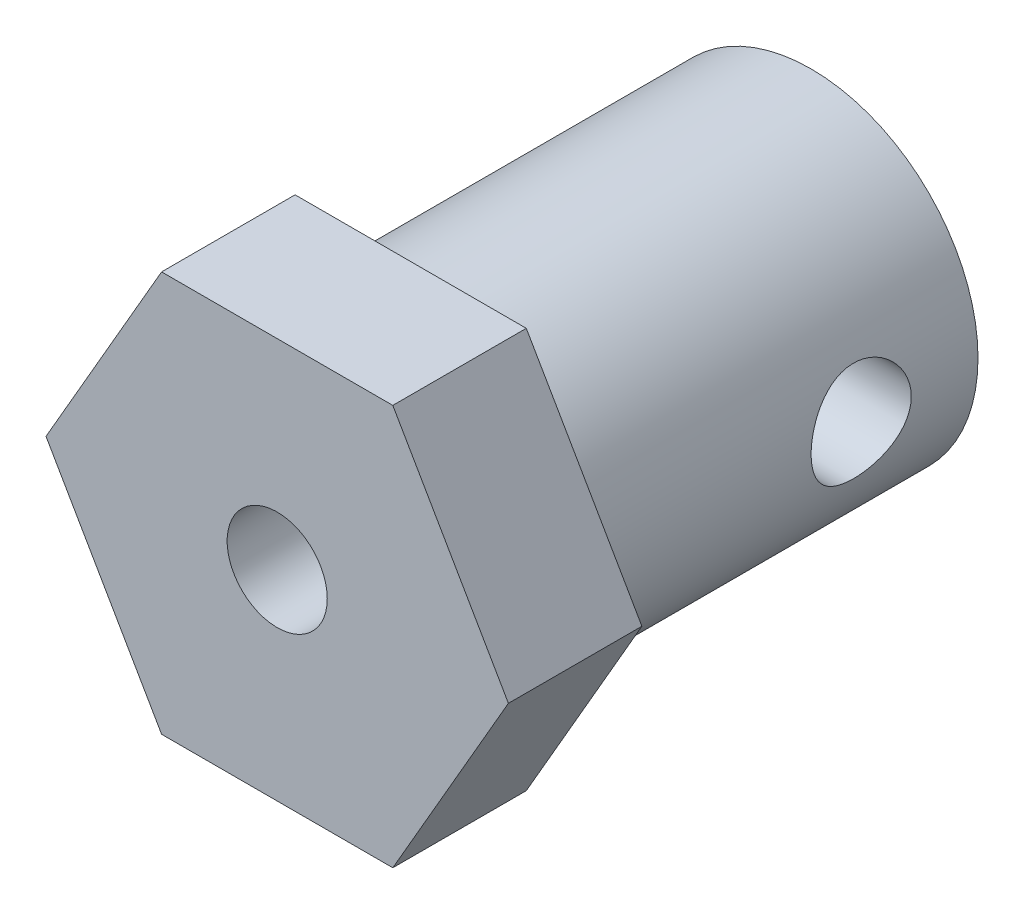
SolidWorks part; units mm, degrees
ref_plane "Alzado" through (0, 0, 0) normal (0, 0, 1) x (1, 0, 0)
ref_plane "Planta" through (0, 0, 0) normal (0, 1, 0) x (1, 0, 0)
ref_plane "Vista lateral" through (0, 0, 0) normal (1, 0, 0) x (0, 0, -1)
sketch "Croquis2" plane through (0, 0, 0) normal (0, 0, 1) x (1, 0, 0)
  line L1 (3.4641, 6) -> (-3.4641, 6)
  line L2 (-3.4641, 6) -> (-6.9282, 0)
  line L3 (-6.9282, 0) -> (-3.4641, -6)
  line L4 (-3.4641, -6) -> (3.4641, -6)
  line L5 (3.4641, -6) -> (6.9282, 0)
  line L6 (6.9282, 0) -> (3.4641, 6)
  circle A0 centre (0, 0) radius 6 construction
  circle A1 centre (0, 0) radius 1.5
  dimension "D1" = 3
  dimension "D2" = 12
extrude "Saliente-Extruir1" add sketch "Croquis2" along normal blind 4
sketch "Croquis3" plane through (0, 0, 0) normal (0, 0, -1) x (-1, 0, 0)
  circle A0 centre (0, 0) radius 5
  circle A1 centre (0, 0) radius 2.5
  dimension "D1" = 10
  dimension "D2" = 5
extrude "Saliente-Extruir2" add sketch "Croquis3" along normal blind 12 contours A0 | A1
sketch "Croquis4" plane through (0, 0, 0) normal (1, 0, 0) x (0, 0, -1)
  line L0 (0, 0) -> (16.2588, 0) construction
  circle A0 centre (8.5, 0) radius 1.5
  dimension "D2" = 3
  dimension "D1" = 8.5
extrude "Cortar-Extruir1" cut sketch "Croquis4" along normal blind 10
